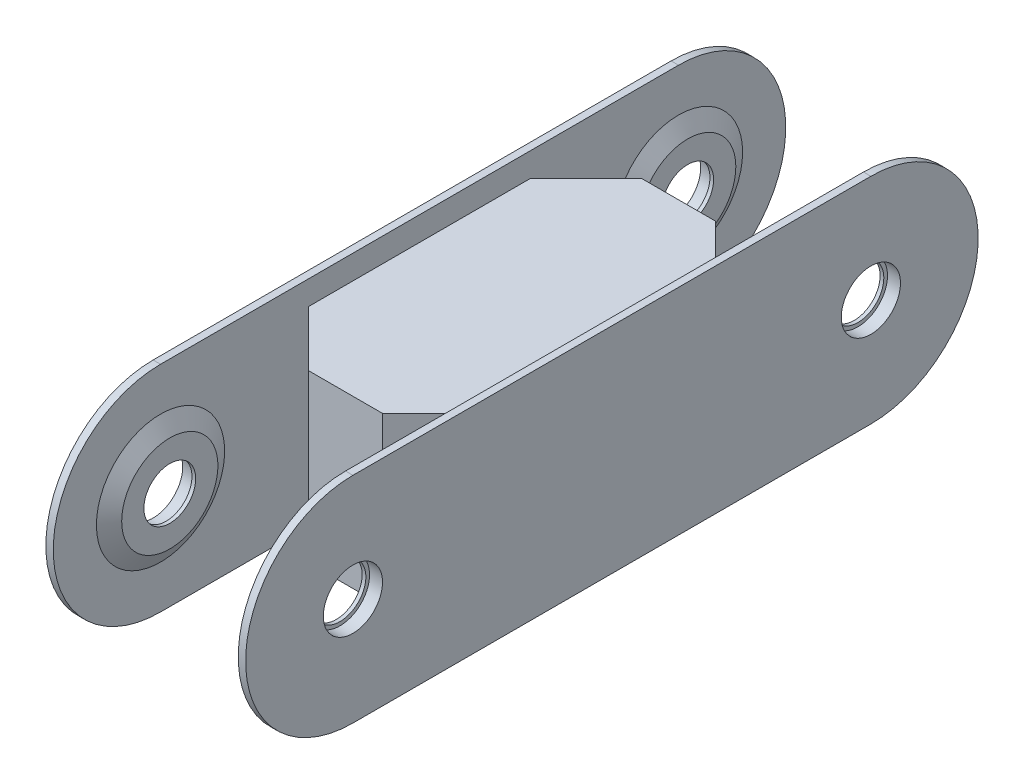
SolidWorks part; units mm, degrees
ref_plane "Front Plane" through (0, 0, 0) normal (0, 0, 1) x (1, 0, 0)
ref_plane "Top Plane" through (0, 0, 0) normal (0, 1, 0) x (1, 0, 0)
ref_plane "Right Plane" through (0, 0, 0) normal (1, 0, 0) x (0, 0, -1)
sketch "Sketch1" plane through (0, 0, 0) normal (0, 1, 0) x (1, 0, 0)
  line L1 (-50, -90) -> (50, -90)
  line L2 (-50, -90) -> (-50, 90)
  line L3 (-50, 90) -> (50, 90)
  line L4 (50, -90) -> (50, 90)
  line L5 (-50, -90) -> (50, 90) construction
  line L6 (-50, 90) -> (50, -90) construction
  point P0 (0, 0)
  dimension "D1" = 100
  dimension "D2" = 180
extrude "Boss-Extrude1" add sketch "Sketch1" along normal blind 90 contours L3 L4 L1 L2
chamfer "Chamfer1" distance 30 angle 45 4 edges at (-50, 45, -90) (50, 45, -90) (-50, 45, 90) (50, 45, 90)
sketch "Sketch2" plane through (50, 0, 0) normal (1, 0, 0) x (0, 0, -1)
  line L0 (90, 45) -> (-90, 45) construction
  line L1 (90, 90) -> (90, 0) construction
  line L2 (-90, 90) -> (-90, 0) construction
  line L3 (-140, 45) -> (140, 45) construction
  line L4 (-140, 103) -> (140, 103)
  line L5 (-140, -13) -> (140, -13)
  arc A0 (-140, 103) -> (-140, -13) centre (-140, 45) ccw
  arc A1 (140, -13) -> (140, 103) centre (140, 45) ccw
  point P8 (0, 45)
  point P13 (0, 0)
  point P14 (-104.4436, 101.7542)
  dimension "D2" = 58
  dimension "D1" = 280
extrude "Boss-Extrude2" add sketch "Sketch2" along normal blind 4
ref_plane "Plane1" through (45, 0, 0) normal (-1, 0, 0) x (0, 0, 1)
sketch "Sketch3" plane through (45, 0, 0) normal (-1, 0, 0) x (0, 0, 1)
  circle A0 centre (140, 45) radius 16
  circle A1 centre (140, 45) radius 26
  dimension "D1" = 32
  dimension "D2" = 52
extrude "Boss-Extrude3" add sketch "Sketch3" against normal up to surface (5 mm away) draft 60 contours A1 up to face at (50, 45, 0) draft outward yes
sketch "Sketch4" plane through (45, 0, 0) normal (-1, 0, 0) x (0, 0, 1)
  circle A0 centre (140, 45) radius 14
  dimension "D1" = 28
extrude "Cut-Extrude1" cut sketch "Sketch4" against normal blind 2
sketch "Sketch5" plane through (47, 0, 0) normal (-1, 0, 0) x (0, 0, 1)
  circle A0 centre (140, 45) radius 16
  dimension "D1" = 32
extrude "Cut-Extrude2" cut sketch "Sketch5" against normal through all
mirror "Mirror1" about plane through (0, 0, 0) normal (0, 0, 1) of "Cut-Extrude2", "Cut-Extrude1", "Boss-Extrude3"
mirror "Mirror2" about plane through (0, 0, 0) normal (1, 0, 0) of "Mirror1", "Cut-Extrude2", "Cut-Extrude1", "Boss-Extrude3", "Boss-Extrude2"
